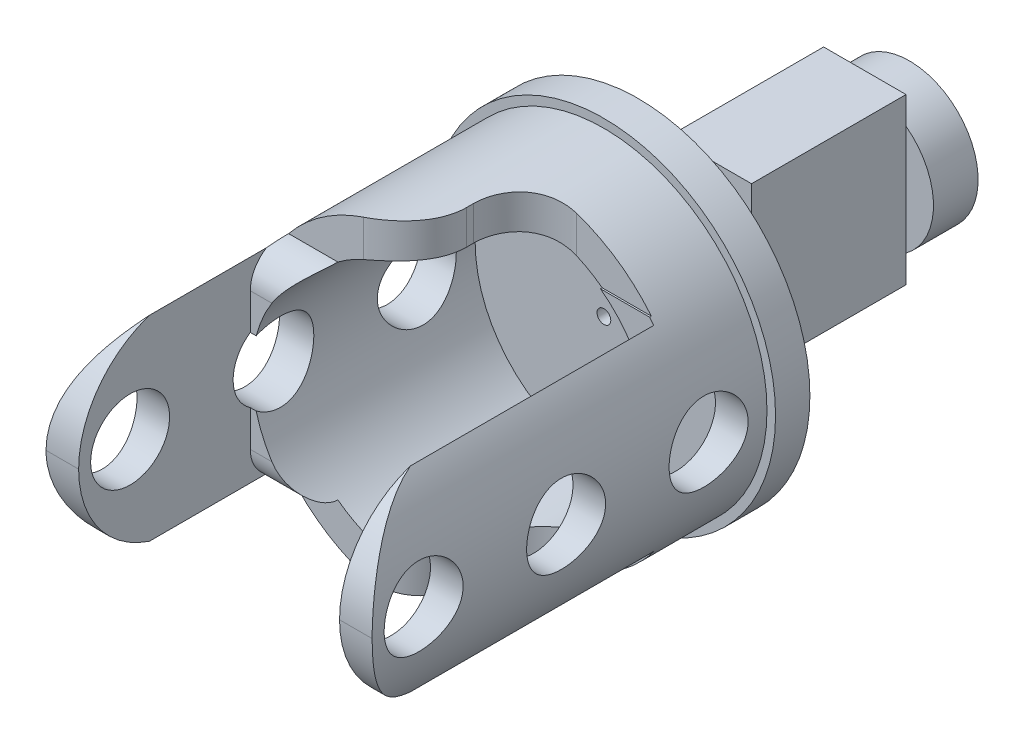
SolidWorks part; units mm, degrees
material "ABS"
ref_plane "Plan de face" through (0, 0, 0) normal (0, 0, 1) x (1, 0, 0)
ref_plane "Plan de dessus" through (0, 0, 0) normal (0, 1, 0) x (1, 0, 0)
ref_plane "Plan de droite" through (0, 0, 0) normal (1, 0, 0) x (0, 0, -1)
sketch "Esquisse1" plane through (0, 0, 0) normal (0, 0, 1) x (1, 0, 0)
  circle A0 centre (0, 0) radius 50
  dimension "D1" = 100
extrude "Boss.-Extru.1" add sketch "Esquisse1" along normal blind 10
sketch "Esquisse2" plane through (0, 0, 0) normal (0, 0, -1) x (-1, 0, 0)
  circle A0 centre (0, 0) radius 47.5
  dimension "D1" = 95
extrude "Enlèv. mat.-Extru.1" cut sketch "Esquisse2" against normal blind 5
sketch "Esquisse6" plane through (0, 0, 10) normal (0, 0, 1) x (1, 0, 0)
  line L0 (0, 0) -> (0, 47.5) construction
  line L1 (0, 47.5) -> (0, -47.5) construction
  line L2 (-22.5, 30) -> (-22.5, -30) construction
  line L3 (-22.5, 30) -> (-36.8273, 30)
  line L4 (-22.5, -30) -> (-36.8273, -30)
  line L5 (22.5, -30) -> (36.8273, -30)
  line L6 (22.5, 30) -> (36.8273, 30)
  circle A0 centre (0, 0) radius 2
  circle A1 centre (0, 0) radius 47.5
  circle A2 centre (0, 0) radius 37.5
  circle A3 centre (0, 0) radius 50 construction
  dimension "D1" = 4
  dimension "D2" = 2.5
  dimension "D3" = 10
  dimension "D4" = 60
extrude "Boss.-Extru.4" add sketch "Esquisse6" along normal blind 115 contours A2 L3 A1 L4 | A2 L5 A1 L6 region at (-38.1648, 0, 10) region at (38.1648, 0, 10)
sketch "Esquisse7" plane through (0, 0, 5) normal (0, 0, -1) x (-1, 0, 0)
  circle A0 centre (0, 0) radius 2
  dimension "D1" = 4
extrude "Enlèv. mat.-Extru.2" cut sketch "Esquisse7" against normal blind 100
sketch "Esquisse12" plane through (0, 0, 10) normal (0, 0, 1) x (1, 0, 0)
  line L1 (-3.6437, 25.162) -> (0, 25.162)
  line L2 (-3.6437, 25.162) -> (-3.6437, 15.1247)
  line L3 (-3.6437, 15.1247) -> (0, 15.1247)
  line L4 (0, 25.162) -> (0, 15.1247)
extrude "Boss.-Extru.7" add sketch "Esquisse12" along normal blind 116
sketch "Esquisse14" plane through (0, 0, 0) normal (1, 0, 0) x (0, 0, -1)
  line L0 (-125, 0) -> (-10, 0) construction
  line L1 (-125, 30) -> (-125, -30) construction
  line L2 (-10, 50) -> (-10, -50) construction
  circle A0 centre (-110, 0) radius 11.5
  circle A2 centre (-68.5, 0) radius 11.5
  circle A3 centre (-27, 0) radius 11.5
  dimension "D4" = 23
  dimension "D5" = 23
  dimension "D6" = 23
  dimension "D1" = 100
  dimension "D2" = 17
  dimension "D3" = 41.5
extrude "Enlèv. mat.-Extru.3" cut sketch "Esquisse14" against normal through all both and the other way through all
sketch "Esquisse15" plane through (0, 0, 126) normal (0, 0, 1) x (1, 0, 0)
  line L1 (0, 15.1247) -> (-3.6437, 15.1247)
  line L2 (0, 15.1247) -> (0, 25.162)
  line L3 (0, 25.162) -> (-3.6437, 25.162)
  line L4 (-3.6437, 15.1247) -> (-3.6437, 25.162)
extrude "Enlèv. mat.-Extru.4" cut sketch "Esquisse15" against normal blind 116
sketch "Esquisse16" plane through (0, 0, 5) normal (0, 0, -1) x (-1, 0, 0)
  circle A0 centre (0, 0) radius 20
  circle A1 centre (0, 0) radius 2
  dimension "D1" = 40
extrude "Boss.-Extru.8" add sketch "Esquisse16" along normal blind 16
sketch "Esquisse17" plane through (0, 0, -11) normal (0, 0, -1) x (-1, 0, 0)
  line L0 (0, 0) -> (0, 20) construction
  line L1 (0, 20) -> (0, -20) construction
  line L2 (0, 0) -> (20, 0) construction
  line L3 (20, 0) -> (-20, 0) construction
  line L4 (0, 20) -> (1.98, 14.8687)
  line L5 (0, 20) -> (-1.98, 14.8687)
  line L6 (-0.9649, 14.9689) -> (-3.9011, 19.6158)
  line L7 (-3.9011, 19.6158) -> (-4.8485, 14.1948)
  line L8 (-3.9011, 19.6158) -> (0, 0) construction
  line L9 (0, 0) -> (3.9011, -19.6158) construction
  line L10 (-7.6524, 18.4781) -> (0, 0) construction
  line L11 (-11.1097, 16.6305) -> (0, 0) construction
  line L12 (-14.1402, 14.1441) -> (0, 0) construction
  line L13 (0, 0) -> (-16.6275, 11.1143) construction
  line L14 (0, 0) -> (-18.476, 7.6575) construction
  line L15 (0, 0) -> (-19.6148, 3.9065) construction
  line L16 (-9.9008, 11.2683) -> (-11.1097, 16.6305)
  line L17 (-11.1097, 16.6305) -> (-6.6069, 13.4666)
  line L18 (-11.2656, 9.9039) -> (-16.6275, 11.1143)
  line L19 (-16.6275, 11.1143) -> (-13.4647, 6.6107)
  line L20 (-14.9687, 0.9691) -> (-19.6148, 3.9065)
  line L21 (-19.6148, 3.9065) -> (-14.1934, 4.8524)
  line L22 (-7.6524, 18.4781) -> (-3.8597, 14.4949)
  line L23 (-7.6524, 18.4781) -> (-7.5184, 12.9797)
  line L24 (-14.1402, 14.1441) -> (-9.1121, 11.9151)
  line L25 (-14.1402, 14.1441) -> (-11.9126, 9.1154)
  line L26 (-18.476, 7.6575) -> (-14.4938, 3.8637)
  line L27 (-18.476, 7.6575) -> (-12.9777, 7.522)
  line L28 (-20, 0) -> (-14.8675, 1.9891)
  line L29 (-20, 0) -> (-14.8675, -1.9891)
  line L30 (-14.9687, -0.9691) -> (-19.6148, -3.9065)
  line L31 (-19.6148, -3.9065) -> (-14.1934, -4.8524)
  line L32 (-18.476, -7.6575) -> (-14.4938, -3.8637)
  line L33 (-18.476, -7.6575) -> (-12.9777, -7.522)
  line L34 (-16.6275, -11.1143) -> (-13.4647, -6.6107)
  line L35 (-11.2656, -9.9039) -> (-16.6275, -11.1143)
  line L36 (-14.1402, -14.1441) -> (-11.9126, -9.1154)
  line L37 (-14.1402, -14.1441) -> (-9.1121, -11.9151)
  line L38 (-9.9008, -11.2683) -> (-11.1097, -16.6305)
  line L39 (-11.1097, -16.6305) -> (-6.6069, -13.4666)
  line L40 (-7.6524, -18.4781) -> (-7.5184, -12.9797)
  line L41 (-7.6524, -18.4781) -> (-3.8597, -14.4949)
  line L42 (-3.9011, -19.6158) -> (-4.8485, -14.1948)
  line L43 (-0.9649, -14.9689) -> (-3.9011, -19.6158)
  line L44 (0, -20) -> (-1.98, -14.8687)
  line L45 (0, -20) -> (1.98, -14.8687)
  line L46 (0.9649, -14.9689) -> (3.9011, -19.6158)
  line L47 (3.9011, -19.6158) -> (4.8485, -14.1948)
  line L48 (7.6524, -18.4781) -> (3.8597, -14.4949)
  line L49 (7.6524, -18.4781) -> (7.5184, -12.9797)
  line L50 (11.1097, -16.6305) -> (6.6069, -13.4666)
  line L51 (9.9008, -11.2683) -> (11.1097, -16.6305)
  line L52 (14.1402, -14.1441) -> (9.1121, -11.9151)
  line L53 (14.1402, -14.1441) -> (11.9126, -9.1154)
  line L54 (11.2656, -9.9039) -> (16.6275, -11.1143)
  line L55 (16.6275, -11.1143) -> (13.4647, -6.6107)
  line L56 (18.476, -7.6575) -> (12.9777, -7.522)
  line L57 (18.476, -7.6575) -> (14.4938, -3.8637)
  line L58 (19.6148, -3.9065) -> (14.1934, -4.8524)
  line L59 (14.9687, -0.9691) -> (19.6148, -3.9065)
  line L60 (20, 0) -> (14.8675, -1.9891)
  line L61 (20, 0) -> (14.8675, 1.9891)
  line L62 (14.9687, 0.9691) -> (19.6148, 3.9065)
  line L63 (19.6148, 3.9065) -> (14.1934, 4.8524)
  line L64 (18.476, 7.6575) -> (14.4938, 3.8637)
  line L65 (18.476, 7.6575) -> (12.9777, 7.522)
  line L66 (16.6275, 11.1143) -> (13.4647, 6.6107)
  line L67 (11.2656, 9.9039) -> (16.6275, 11.1143)
  line L68 (14.1402, 14.1441) -> (11.9126, 9.1154)
  line L69 (14.1402, 14.1441) -> (9.1121, 11.9151)
  line L70 (9.9008, 11.2683) -> (11.1097, 16.6305)
  line L71 (11.1097, 16.6305) -> (6.6069, 13.4666)
  line L72 (7.6524, 18.4781) -> (7.5184, 12.9797)
  line L73 (7.6524, 18.4781) -> (3.8597, 14.4949)
  line L74 (3.9011, 19.6158) -> (4.8485, 14.1948)
  line L75 (0.9649, 14.9689) -> (3.9011, 19.6158)
  line L76 (0, 20) -> (1.98, 14.8687)
  circle A0 centre (0, 0) radius 20
  circle A1 centre (0, 0) radius 2
  circle A2 centre (0, 0) radius 15
  circle M45 centre (0, 0) radius 20
  dimension "D4" = 1.98
  dimension "D5" = 3.96
  dimension "D6" = 1.02
  dimension "D8" = 1.02
extrude "Enlèv. mat.-Extru.7" cut sketch "Esquisse17" against normal blind 16 contours L30 L29 M45 | L32 L31 M45 | L34 L33 M45 | L36 L35 M45 | L38 L37 M45 | L40 L39 M45 | L42 L41 M45 | L44 L43 M45 | L46 L45 M45 | L48 L47 M45 | L50 L49 M45 | L52 L51 M45 | L54 L53 M45 | L56 L55 M45 | L58 L57 M45 | L60 L59 M45 | L62 L61 M45 | L64 L63 M45 | L66 L65 M45 | L68 L67 M45 | L70 L69 M45 | L72 L71 M45 | L74 L73 M45 | L4 L75 M45 | L6 L5 M45 | L22 L7 M45 | L23 L17 M45 | L24 L16 M45 | L25 L18 M45 | L27 L19 M45 | L26 L21 M45 | L28 L20 M45 region at (-1.8282, 18.5572, -11) region at (1.8282, 18.5572, -11) region at (-5.4138, 17.8474, -11) region at (5.4138, 17.8474, -11) region at (-8.7896, 16.4494, -11) region at (8.7896, 16.4494, -11) region at (-11.8272, 14.4163, -11) region at (11.8272, 14.4163, -11) region at (-14.413, 11.8311, -11) region at (14.413, 11.8311, -11) region at (-16.447, 8.7941, -11) region at (16.447, 8.7941, -11) region at (-17.8459, 5.4187, -11) region at (17.8459, 5.4187, -11) region at (-18.5577, 1.832, -11) region at (18.5577, 1.832, -11) region at (-18.5577, -1.832, -11) region at (18.5577, -1.832, -11) region at (-17.8459, -5.4187, -11) region at (17.8459, -5.4187, -11) region at (-16.447, -8.7941, -11) region at (16.447, -8.7941, -11) region at (-14.413, -11.8311, -11) region at (14.413, -11.8311, -11) region at (-11.8272, -14.4163, -11) region at (11.8272, -14.4163, -11) region at (-8.7896, -16.4494, -11) region at (8.7896, -16.4494, -11) region at (-5.4138, -17.8474, -11) region at (5.4138, -17.8474, -11) region at (-1.8282, -18.5572, -11) region at (1.8282, -18.5572, -11)
fillet "Congé3" radius 30 4 edges at (29.6636, -30, 125) (-29.6636, -30, 125) (-29.6636, 30, 125) (29.6636, 30, 125)
sketch "Esquisse18" plane through (0, 0, 10) normal (0, 0, 1) x (1, 0, 0)
  line L0 (35, 0) -> (35, 35.7071)
  line L1 (35, 35.7071) -> (35, -35.7071)
  line L2 (35, -15) -> (37, -15)
  line L3 (35, 35.7071) -> (32, 35.7071)
  line L4 (35, 35.7071) -> (35, -35.7071)
  line L5 (35, -35.7071) -> (32, -35.7071)
  line L6 (32, 35.7071) -> (32, -35.7071)
  line L7 (35, 35.7071) -> (37, 35.7071)
  line L8 (35, 35.7071) -> (35, -35.7071)
  line L9 (35, -35.7071) -> (37, -35.7071)
  line L10 (37, 35.7071) -> (37, -35.7071)
  line L11 (35, 0) -> (37, 0)
  line L12 (35, 0) -> (35, 15)
  line L13 (35, 15) -> (37, 15)
  line L14 (37, 0) -> (37, 15)
  line L15 (37, 0) -> (32, 0)
  line L16 (32, 0) -> (34.5, 0)
  line L18 (38, -17) -> (31, -17)
  line L19 (38, -17) -> (38, 17)
  line L20 (38, 17) -> (31, 17)
  line L21 (31, -17) -> (31, 17)
  line L22 (38, -17) -> (31, 17) construction
  line L23 (38, 17) -> (31, -17) construction
  circle A0 centre (0, 0) radius 35
  circle A1 centre (0, 0) radius 50 construction
  arc M17 (22.5, -30) -> (22.5, 30) centre (0, 0) ccw
  dimension "D1" = 70
  dimension "D2" = 3
  dimension "D3" = 2
  dimension "D4" = 15
  dimension "D5" = 2.5
  dimension "D6" = 1
  dimension "D7" = 2
extrude "Enlèv. mat.-Extru.8" cut sketch "Esquisse18" along normal blind 150 contours L19 L20 L10 L18 M17 | L0 L11 L10 M17 | L13 L0 L10 M17 | L10 L20 L8 L13 | L11 L1 L10 M17 | L10 L1 L2 M17 | L18 L10 L2 L1 | L8 L20 L0 M17 | L18 L1 M17 region at (35.8843, -5.3474, 10) region at (35.8843, 5.3474, 10) region at (34.487, 15.8492, 10) region at (36.2519, 12.1846, 10) region at (36.2519, -12.1846, 10) region at (34.487, -15.8492, 10) region at (36, 16, 10) region at (37.5408, 0, 10) region at (36, -16, 10)
sketch "Esquisse21" plane through (38, 0, 0) normal (-1, 0, 0) x (0, 0, 1)
  line L0 (68.5, 0) -> (33.5, 0) construction
  line L1 (95, 30) -> (10, 30) construction
  line L2 (33.5, 30) -> (125, 30)
  line L3 (33.5, 30) -> (33.5, 0)
  line L4 (33.5, 0) -> (125, 0)
  line L5 (125, 30) -> (125, 0)
  line L7 (33.5, 0) -> (95, 0)
  line L8 (33.5, 0) -> (33.5, -30)
  line L9 (33.5, -30) -> (95, -30)
  line L10 (95, 0) -> (95, -30)
  line L11 (95, 0) -> (125, 0)
  line L12 (95, 0) -> (95, -30)
  line L13 (95, -30) -> (125, -30)
  line L14 (125, 0) -> (125, -30)
  line M2 (119.7184, 17) -> (10, 17)
  line M4 (10, -17) -> (119.7184, -17)
  arc M5 (119.7184, -17) -> (125, 0) centre (95, 0) ccw
  arc M6 (125, 0) -> (119.7184, 17) centre (95, 0) ccw
  circle M7 centre (110, 0) radius 11.5
  circle M8 centre (68.5, 0) radius 11.5
  circle M9 centre (27, 0) radius 11.5
  dimension "D1" = 35
extrude "Enlèv. mat.-Extru.9" cut sketch "Esquisse21" along normal blind 20 contours L5 L2 L3 M2 M6 | L4 L3 M9 M8 M7 M6 M2 | L10 L4 L8 M8 M9 M4 | L4 L10 M4 M5 M7 | L10 L8 L9 M4 | L14 L10 L13 M5 M4 region at (38, 23.2478, 80.2943) region at (38, 9.9281, 75.5662) region at (38, -8.7985, 123.3199) region at (38, -22.7664, 110.9241) region at (38, -0.6381, 47.75) region at (38, -23.5, 64.25)
sketch "Esquisse22" plane through (0, 0, -11) normal (0, 0, -1) x (-1, 0, 0)
  circle A0 centre (0, 0) radius 15
  dimension "D1" = 30
extrude "Boss.-Extru.9" add sketch "Esquisse22" along normal blind 10
sketch "Esquisse23" plane through (0, 0, -21) normal (0, 0, -1) x (-1, 0, 0)
  line L1 (-12, -24) -> (12, -24)
  line L2 (-12, -24) -> (-12, 24)
  line L3 (-12, 24) -> (12, 24)
  line L4 (12, -24) -> (12, 24)
  line L5 (-12, -24) -> (12, 24) construction
  line L6 (-12, 24) -> (12, -24) construction
  point P0 (0, 0)
  dimension "D1" = 48
  dimension "D2" = 24
extrude "Boss.-Extru.10" add sketch "Esquisse23" along normal blind 45
sketch "Esquisse24" plane through (0, 0, -66) normal (0, 0, -1) x (-1, 0, 0)
  circle A0 centre (0, 0) radius 20
extrude "Boss.-Extru.11" add sketch "Esquisse24" along normal blind 5
sketch "Esquisse25" plane through (0, 0, -71) normal (0, 0, -1) x (-1, 0, 0)
  circle A0 centre (0, 0) radius 20
  circle A1 centre (0, 0) radius 11.5
  dimension "D1" = 23
extrude "Boss.-Extru.12" add sketch "Esquisse25" along normal blind 8
ref_plane "Plan2" through (-37.5, 0, 125) normal (-1, 0, 0) x (0, 0, 1)
sketch "Esquisse27" plane through (-37.5, 0, 125) normal (-1, 0, 0) x (0, 0, 1)
  line L1 (0, 0) -> (-50, 0)
  line L2 (0, 0) -> (0, 30)
  line L3 (0, 30) -> (-50, 30)
  line L4 (-50, 0) -> (-50, 30)
  line L5 (0, 0) -> (-50, 0)
  line L6 (0, 0) -> (0, -30)
  line L7 (0, -30) -> (-50, -30)
  line L8 (-50, 0) -> (-50, -30)
  dimension "D1" = 50
  dimension "D2" = 30
  dimension "D3" = 30
extrude "Enlèv. mat.-Extru.10" cut sketch "Esquisse27" against normal blind 20 and the other way blind 0.5 contours L1 L8 L7 L6 | L4 L1 L2 L3 region at (-37.5, -15, 100) region at (-37.5, 15, 100)
fillet "Congé5" radius 10 2 edges at (-29.6636, 30, 75) (-29.6636, -30, 75)
sketch "Esquisse28" plane through (0, 0, 10) normal (0, 0, 1) x (1, 0, 0)
  line L0 (-36.8273, 30) -> (-22.5, 30)
  line L1 (22.5, 30) -> (36.8273, 30)
  line L2 (-36.8273, -30) -> (-22.5, -30)
  line L3 (22.5, -30) -> (36.8273, -30)
  circle A0 centre (0, 0) radius 47.5
  circle A1 centre (0, 0) radius 37.5
  line M5 (22.5, 30) -> (36.8273, 30)
  line M7 (36.8273, -30) -> (22.5, -30)
  line M13 (-22.5, -30) -> (-36.8273, -30)
  line M15 (-36.8273, 30) -> (-22.5, 30)
  dimension "D1" = 95
extrude "Boss.-Extru.13" add sketch "Esquisse28" along normal blind 23 contours A1 A0 M5 M15 | A1 A0 M13 M7 region at (0, 38.5359, 10) region at (0, -38.5359, 10)
sketch "Esquisse29" plane through (0, 0, 33) normal (0, 0, 1) x (1, 0, 0)
  line L0 (0, 47.5) -> (0, 37.5)
  line L1 (0, 37.5) -> (0, -37.5)
  line L2 (0, -37.5) -> (0, -47.5)
  line L3 (-36.8273, 30) -> (-22.5, 30)
  line L4 (-36.8273, -30) -> (-22.5, -30)
  arc A0 (36.8273, 30) -> (-36.8273, 30) centre (0, 0) ccw construction
  arc A1 (22.5, 30) -> (-22.5, 30) centre (0, 0) ccw construction
  arc A2 (-22.5, -30) -> (22.5, -30) centre (0, 0) ccw construction
  arc A3 (-36.8273, -30) -> (36.8273, -30) centre (0, 0) ccw construction
  arc A4 (33.4253, 17) -> (33.4253, -17) centre (0, 0) ccw construction
  arc A5 (-31.7214, -20) -> (-22.5, -30) centre (0, 0) ccw construction
  circle A6 centre (0, 0) radius 37.5
  circle A7 centre (0, 0) radius 47.5
  arc M2 (-22.5, 30) -> (22.5, 30) centre (0, 0) cw
  arc M4 (36.8273, 30) -> (-36.8273, 30) centre (0, 0) ccw
  line M5 (-36.8273, 30) -> (-22.5, 30)
extrude "Boss.-Extru.15" add sketch "Esquisse29" along normal blind 32 contours L4 A7 L2 A6 | L0 M4 M5 M2 region at (-16.1789, 38.5359, 33) region at (-16.1789, -38.5359, 33)
fillet "Congé6" radius 15 1 edges at (0, -42.5, 33)
fillet "Congé7" radius 15 1 edges at (0, -42.5, 65)
fillet "Congé8" radius 15 1 edges at (0, 42.5, 65)
fillet "Congé9" radius 15 1 edges at (0, 42.5, 33)
